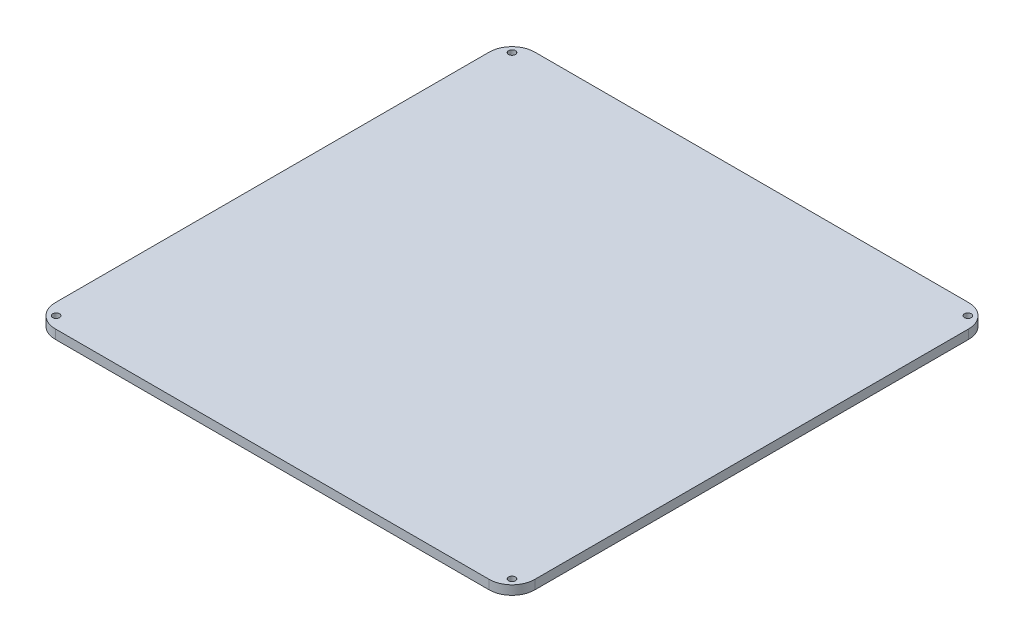
SolidWorks part; units mm, degrees
ref_plane "Front Plane" through (0, 0, 0) normal (0, 0, 1) x (1, 0, 0)
ref_plane "Top Plane" through (0, 0, 0) normal (0, 1, 0) x (1, 0, 0)
ref_plane "Right Plane" through (0, 0, 0) normal (1, 0, 0) x (0, 0, -1)
sketch "Sketch1" plane through (0, 0, 0) normal (0, 1, 0) x (1, 0, 0)
  line L0 (-101, -101) -> (-101, 101)
  line L5 (-105, -105) -> (105, -105)
  line L6 (-105, -105) -> (-105, 105)
  line L7 (-105, 105) -> (105, 105)
  line L8 (105, -105) -> (105, 105)
  line L9 (-101, 101) -> (101, 101)
  line L10 (101, -101) -> (101, 101)
  line L11 (-101, -101) -> (101, -101)
  line L12 (-101, 101) -> (-99.8333, 99.8333) construction
  line L13 (-55, 0) -> (55, 0) construction
  line L14 (-101, -101) -> (-99.8333, -99.8333) construction
  line L15 (0, -55) -> (0, 55) construction
  line L16 (101, -101) -> (99.8333, -99.8333) construction
  line L17 (101, 101) -> (99.8333, 99.8333) construction
  circle A1 centre (-99.8333, 99.8333) radius 1.5
  circle A2 centre (-99.8333, -99.8333) radius 1.5
  circle A3 centre (99.8333, -99.8333) radius 1.5
  circle A4 centre (99.8333, 99.8333) radius 1.5
  point P0 (0, 0)
  point P6 (-105, 0)
  point P7 (0, 105)
  point P14 (0, 0)
  dimension "D3" = 4
  dimension "D4" = 3
  dimension "D1" = 210
  dimension "D2" = 210
  dimension "D5" = 1.65
  dimension "D6" = 45
extrude "MainExtrude" add sketch "Sketch1" along normal blind 4 contours L6 L5 L8 L7
extrude "ScrewHoles" cut sketch "Sketch1<6>" along normal up to surface (4 mm away) contours A1 | A2 | A3 | A4 up to face at (0, 4, 0)
sketch "Sketch1<6>" plane through (0, 0, 0) normal (0, 1, 0) x (1, 0, 0) same geometry as "Sketch1"
fillet "RoundedCorners" radius 10 4 edges at (-105, 2, -105) (-105, 2, 105) (105, 2, -105) (105, 2, 105)
